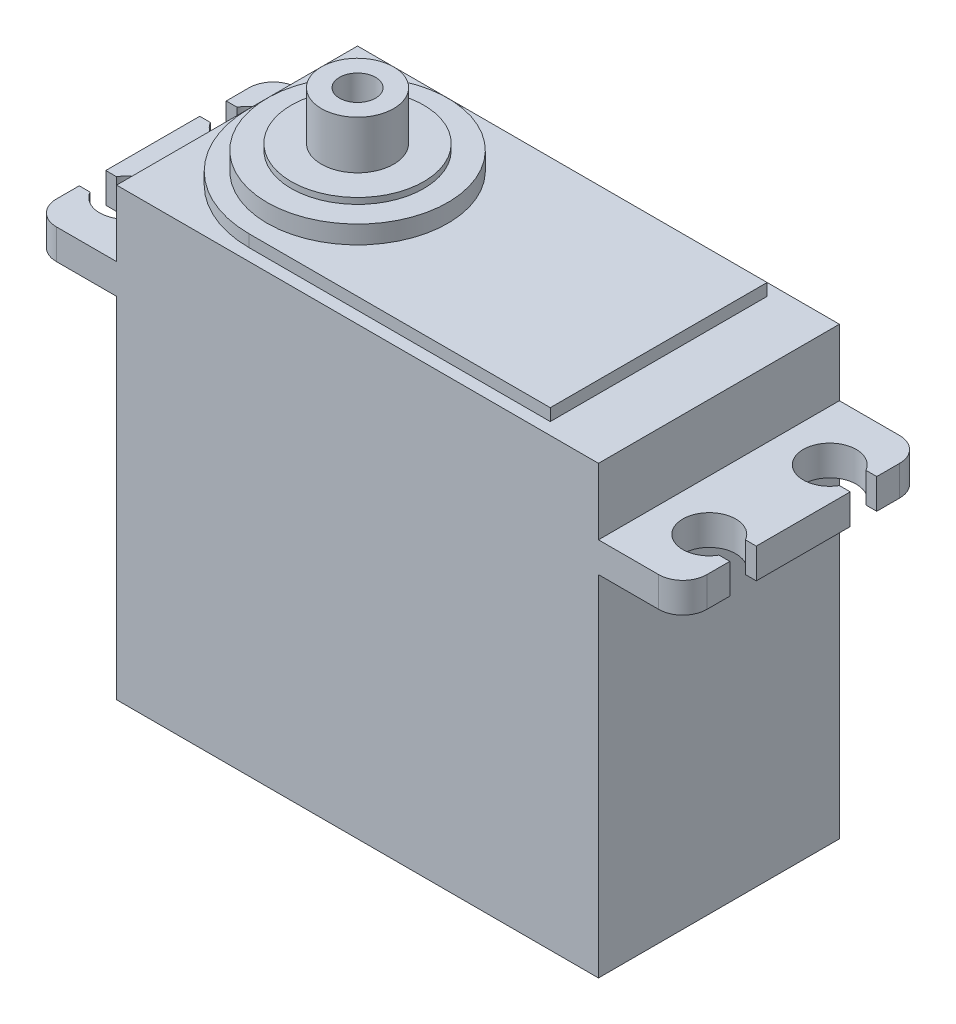
SolidWorks part; units mm, degrees
material "POM 乙缩醛共聚物"
ref_plane "前视基准面" through (0, 0, 0) normal (0, 0, 1) x (1, 0, 0)
ref_plane "上视基准面" through (0, 0, 0) normal (0, 1, 0) x (1, 0, 0)
ref_plane "右视基准面" through (0, 0, 0) normal (1, 0, 0) x (0, 0, -1)
sketch "草图1" plane through (0, 0, 0) normal (0, 1, 0) x (1, 0, 0)
  line L1 (-20, -10) -> (20, -10)
  line L2 (-20, -10) -> (-20, 10)
  line L3 (-20, 10) -> (20, 10)
  line L4 (20, -10) -> (20, 10)
  line L5 (-20, -10) -> (20, 10) construction
  line L6 (-20, 10) -> (20, -10) construction
  point P0 (0, 0)
  dimension "D1" = 40
  dimension "D2" = 20
extrude "凸台-拉伸1" add sketch "草图1" along normal blind 37
ref_plane "基准面1" through (0, 29, 0) normal (0, -1, 0) x (-1, 0, 0)
sketch "草图2" plane through (0, 29, 0) normal (0, -1, 0) x (-1, 0, 0)
  line L1 (27, -10) -> (-27, -10)
  line L2 (27, -10) -> (27, 10)
  line L3 (27, 10) -> (-27, 10)
  line L4 (-27, -10) -> (-27, 10)
  line L5 (27, -10) -> (-27, 10) construction
  line L6 (27, 10) -> (-27, -10) construction
  point P0 (0, 0)
  dimension "D1" = 54
  dimension "D2" = 20
extrude "凸台-拉伸2" add sketch "草图2" against normal blind 2.5
sketch "草图3" plane through (0, 29, 0) normal (0, -1, 0) x (-1, 0, 0)
  line L0 (0, 0) -> (30.7764, 0) construction
  line L1 (0, 14.376) -> (0, -16.6057) construction
  line L2 (-24.2, 5) -> (24.2, 5) construction
  circle A0 centre (24.2, 5) radius 2.2
  circle A1 centre (-24.2, 5) radius 2.2
  circle A2 centre (24.2, -5) radius 2.2
  circle A3 centre (-24.2, -5) radius 2.2
  dimension "D1" = 4.4
  dimension "D2" = 48.4
  dimension "D3" = 10
extrude "切除-拉伸1" cut sketch "草图3" against normal blind 2.5
sketch "草图5" plane through (0, 29, 0) normal (0, -1, 0) x (-1, 0, 0)
  line L0 (-24.2, 5) -> (24.2, 5) construction
  line L1 (0, 14.1298) -> (0, -13.2316) construction
  line L2 (-27, 6.1) -> (-25.5, 6.1)
  line L3 (-27, 10) -> (-27, -10) construction
  line L4 (-25.5, 6.1) -> (-25.5, 3.9)
  line L5 (-25.5, 3.9) -> (-27, 3.9)
  line L6 (-27, 3.9) -> (-27, 6.1)
  line L7 (27, 3.9) -> (27, 6.1)
  line L8 (25.5, 3.9) -> (27, 3.9)
  line L9 (25.5, 6.1) -> (25.5, 3.9)
  line L10 (27, 6.1) -> (25.5, 6.1)
  line L11 (-28.6426, 0) -> (33.6245, 0) construction
  line L12 (25.5, -6.1) -> (25.5, -3.9)
  line L13 (25.5, -3.9) -> (27, -3.9)
  line L14 (27, -3.9) -> (27, -6.1)
  line L15 (27, -6.1) -> (25.5, -6.1)
  line L16 (-25.5, -3.9) -> (-27, -3.9)
  line L17 (-27, -3.9) -> (-27, -6.1)
  line L18 (-25.5, -6.1) -> (-25.5, -3.9)
  line L19 (-27, -6.1) -> (-25.5, -6.1)
  dimension "D1" = 2.2
  dimension "D2" = 1.5
extrude "切除-拉伸2" cut sketch "草图5" against normal blind 2.5
fillet "圆角1" radius 2 4 edges at (27, 30.25, 10) (27, 30.25, -10) (-27, 30.25, 10) (-27, 30.25, -10)
sketch "草图6" plane through (0, 37, 0) normal (0, 1, 0) x (1, 0, 0)
  line L0 (-19.0995, 0) -> (19.3929, 0) construction
  line L1 (-27, -3.9) -> (-27, 3.9) construction
  line L2 (-10, 9) -> (15, 9)
  line L3 (15, 9) -> (15, -9)
  line L4 (15, -9) -> (-10, -9)
  arc A1 (-10, 9) -> (-10, -9) centre (-10, 0) ccw
  dimension "D1" = 17
  dimension "D2" = 9
  dimension "D3" = 15
extrude "凸台-拉伸3" add sketch "草图6" along normal blind 1
sketch "草图7" plane through (0, 38, 0) normal (0, 1, 0) x (1, 0, 0)
  line L0 (-16.7618, 0) -> (14.4634, 0) construction
  line L1 (0, 7.0403) -> (0, -7.5202) construction
  circle A0 centre (-10, 0) radius 7.5
  dimension "D1" = 15
  dimension "D2" = 10
extrude "凸台-拉伸4" add sketch "草图7" along normal blind 1.5
sketch "草图8" plane through (0, 39.5, 0) normal (0, 1, 0) x (1, 0, 0)
  line L0 (-12.6246, 0) -> (13.3069, 0) construction
  line L1 (0, 7.6879) -> (0, -7.8504) construction
  circle A0 centre (-10, 0) radius 5.5
extrude "凸台-拉伸5" add sketch "草图8" along normal blind 0.5
sketch "草图9" plane through (0, 40, 0) normal (0, 1, 0) x (1, 0, 0)
  line L0 (-10.8865, 0) -> (12.7935, 0) construction
  circle A0 centre (-10, 0) radius 3
  dimension "D1" = 6
extrude "凸台-拉伸6" add sketch "草图9" along normal blind 4
sketch "草图10" plane through (0, 44, 0) normal (0, 1, 0) x (1, 0, 0)
  circle A0 centre (-10, 0) radius 1.5
  dimension "D1" = 3
extrude "切除-拉伸3" cut sketch "草图10" against normal blind 5
